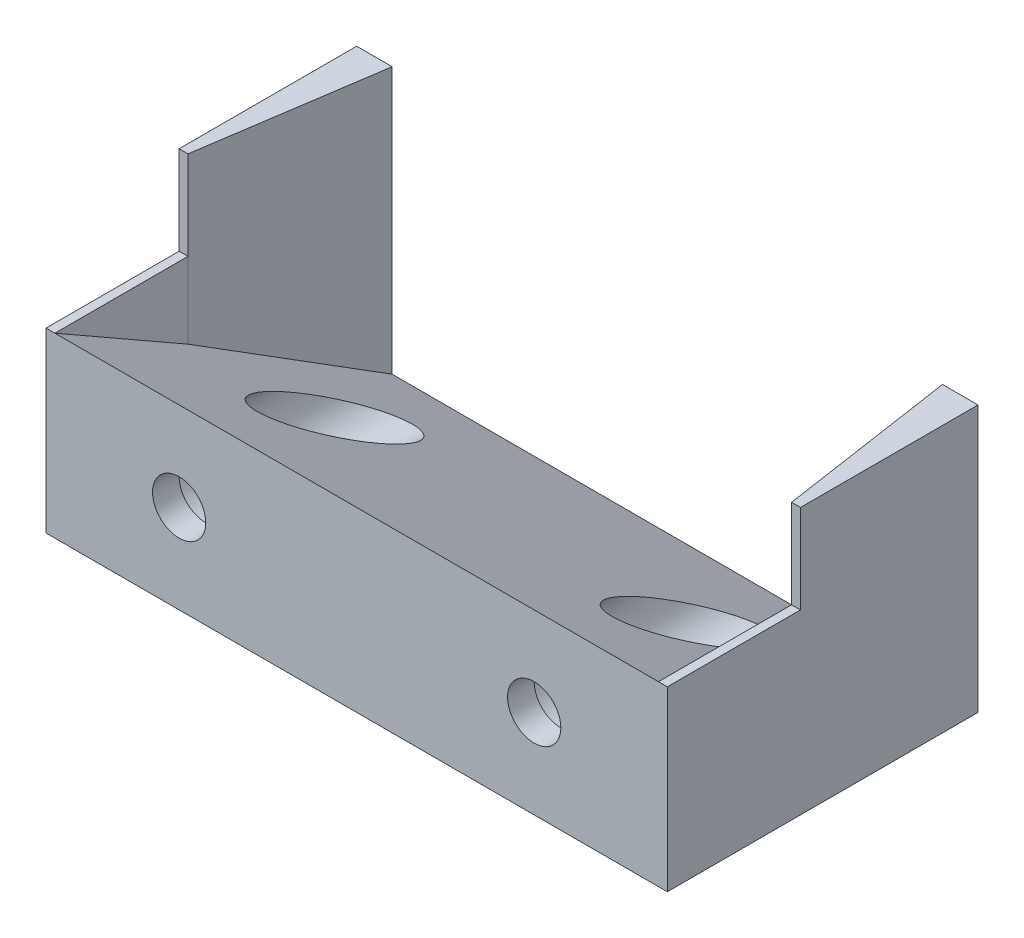
SolidWorks part; units mm, degrees
ref_plane "前视基准面" through (0, 0, 0) normal (0, 0, 1) x (1, 0, 0)
ref_plane "上视基准面" through (0, 0, 0) normal (0, 1, 0) x (1, 0, 0)
ref_plane "右视基准面" through (0, 0, 0) normal (1, 0, 0) x (0, 0, -1)
other "Configuration Table"
sketch "草图1" plane through (0, 0, 0) normal (1, 0, 0) x (0, 0, -1)
  line L0 (0, 0) -> (0, -20)
  line L1 (0, -20) -> (20, -20)
  line L2 (20, -20) -> (0, 0)
  dimension "D1" = 20
  dimension "D2" = 20
extrude "凸台-拉伸2" add sketch "草图1" along normal mid plane 70
sketch "草图4" plane through (0, 0, 0) normal (0, 0, 1) x (1, 0, 0)
  line L1 (-35, 0) -> (35, 0)
  line L2 (-35, 0) -> (-35, -20)
  line L3 (-35, -20) -> (35, -20)
  line L4 (35, 0) -> (35, -20)
extrude "凸台-拉伸3" add sketch "草图4" along normal blind 15
sketch "草图6" plane through (0, -20, 0) normal (0, -1, 0) x (1, 0, 0)
  line L0 (0, 0) -> (0, -50000) construction
  line L17 (-35, -10) -> (-50035, -10) construction
  line L18 (-35, 15) -> (-35, -20) construction
  line L19 (-35, 0) -> (-33, 0)
  line L20 (-35, 0) -> (-35, -20)
  line L21 (-35, -20) -> (-33, -20)
  line L22 (-33, 0) -> (-33, -20)
  line L23 (35, -20) -> (-35, -20) construction
  line L24 (35, 15) -> (35, -20) construction
  line L25 (35, 0) -> (33, 0)
  line L26 (35, 0) -> (35, -20)
  line L27 (35, -20) -> (33, -20)
  line L28 (33, 0) -> (33, -20)
  line L29 (-35, 15) -> (35, 15) construction
  dimension "D1" = 2
  dimension "D2" = 2
  dimension "D3" = 15
  dimension "D4" = 15
extrude "凸台-拉伸5" add sketch "草图6" against normal blind 30
sketch "草图8" plane through (0, 0, 15) normal (0, 0, 1) x (1, 0, 0)
  line L0 (-35, -10) -> (-50035, -10) construction
  line L1 (-35, 0) -> (-35, -20) construction
  line L2 (35, -20) -> (35, 0) construction
  circle A0 centre (-20, -10) radius 3
  circle A1 centre (20, -10) radius 3
  point P4 (-35, -10)
  dimension "D1" = 6
  dimension "D2" = 6
  dimension "D3" = 15
  dimension "D4" = 15
extrude "切除-拉伸3" cut sketch "草图8" against normal through all
sketch "草图9" plane through (0, 0, -20) normal (0, 0, -1) x (-1, 0, 0)
  circle A0 centre (-20, -10) radius 5
  circle A1 centre (20, -10) radius 5
  dimension "D1" = 10
  dimension "D2" = 10
extrude "切除-拉伸4" cut sketch "草图9" against normal blind 50
sketch "草图10" plane through (-33, 0, 0) normal (1, 0, 0) x (0, 0, -1)
  line L0 (-15, 0) -> (20, -20)
  line L1 (20, -20) -> (20, 0)
  line L2 (20, 10) -> (20, -20) construction
  line L3 (20, 0) -> (-15, 0)
extrude "切除-拉伸7" cut sketch "草图10" along normal blind 66
sketch "草图11" plane through (0, 0, 15) normal (0, 0, 1) x (1, 0, 0)
  line L0 (33, 0) -> (-33, 0) construction
  line L1 (-35, -5) -> (35, -5)
  line L2 (-35, -5) -> (-35, -20)
  line L3 (-35, -20) -> (35, -20)
  line L4 (35, -5) -> (35, -20)
  circle A0 centre (-20, -10) radius 3
  circle A1 centre (20, -10) radius 3
  dimension "D1" = 6
  dimension "D2" = 6
  dimension "D3" = 5
extrude "凸台-拉伸7" add sketch "草图11" against normal blind 3
sketch "草图12" plane through (33, 0, 0) normal (-1, 0, 0) x (0, 0, 1)
  line L0 (-20, 10) -> (0, 10)
  line L1 (0, 10) -> (0, 0)
  line L2 (0, 0) -> (15, 0)
  line L3 (15, 0) -> (-20, -20)
  line L4 (15, -20) -> (-20, -20) construction
  line L5 (-20, 10) -> (-20, -20) construction
  line L6 (-20, -20) -> (-20, 10)
extrude "切除-拉伸8" cut sketch "草图12" against normal blind 1
sketch "草图13" plane through (-33, 0, 0) normal (1, 0, 0) x (0, 0, -1)
  line L0 (-15, 0) -> (20, -20)
  line L1 (20, -20) -> (20, 10)
  line L2 (20, 10) -> (0, 10)
  line L3 (0, 10) -> (0, 0)
  line L4 (0, 0) -> (-15, 0)
extrude "切除-拉伸9" cut sketch "草图13" against normal blind 1
sketch "草图14" plane through (0, -20, 0) normal (0, -1, 0) x (1, 0, 0)
  line L0 (-34, -20) -> (-31, -20)
  line L1 (34, -20) -> (-34, -20) construction
  line L2 (-31, -20) -> (-34, 0)
  line L4 (-34, 0) -> (-34, -20)
  line L5 (34, -20) -> (31, -20)
  line L6 (31, -20) -> (34, 0)
  line L7 (34, 0) -> (34, -20)
  dimension "D1" = 3
  dimension "D2" = 3
extrude "凸台-拉伸9" add sketch "草图14" against normal blind 30
